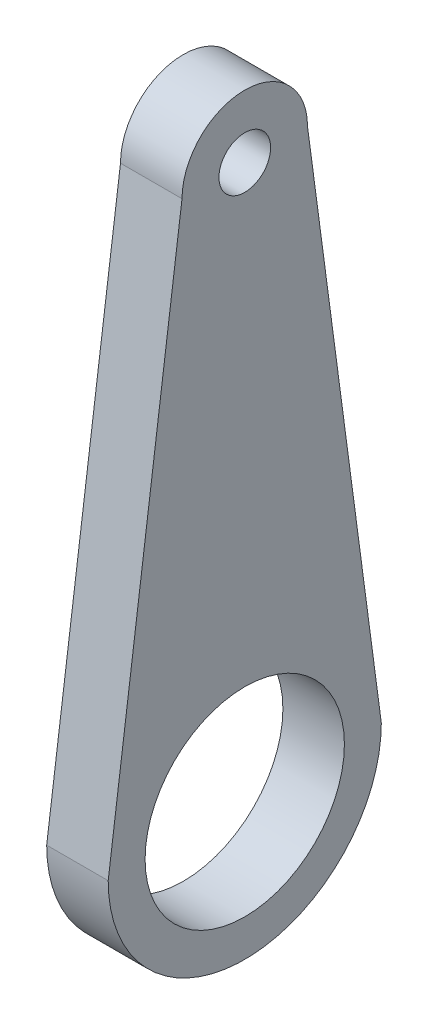
SolidWorks part; units mm, degrees
ref_plane "Front Plane" through (0, 0, 0) normal (1, 0, 0) x (0, 1, 0)
ref_plane "Top Plane" through (0, 0, 0) normal (0, 0, 1) x (0, 1, 0)
ref_plane "Right Plane" through (0, 0, 0) normal (0, 1, 0) x (-1, 0, 0)
sketch "Sketch2" plane through (0, 0, 0) normal (1, 0, 0) x (0, 1, 0)
  line L0 (0, 0) -> (8.1, 0)
  line L3 (42.9, 0) -> (45, 0)
  line L4 (0, 11.1) -> (45, 5.1)
  line L5 (45, -5.1) -> (0, -11.1)
  circle A0 centre (0, 0) radius 8.1
  circle A1 centre (45, 0) radius 2.1
  arc A2 (0, 11.1) -> (0, -11.1) centre (0, 0) ccw
  arc A3 (45, -5.1) -> (45, 5.1) centre (45, 0) ccw
  circle A4 centre (0, 0) radius 11.1 construction
  circle A5 centre (45, 0) radius 5.1 construction
  dimension "D1" = 16.2
  dimension "D2" = 4.2
  dimension "D4" = 3
  dimension "D3" = 3
extrude "Boss-Extrude1" add sketch "Sketch2" along normal mid plane 5 contours L5 A3 L4 A2 A0 A1 region at (0, 19.8667, 0)
sketch "Sketch3" plane through (-2.5, 0, 0) normal (1, 0, 0) x (0, 1, 0)
  circle A0 centre (0, 0) radius 4.25
  dimension "D1" = 8.5
extrude "Cut-Extrude1" [suppressed] cut sketch "Sketch3" along normal blind 0.8
